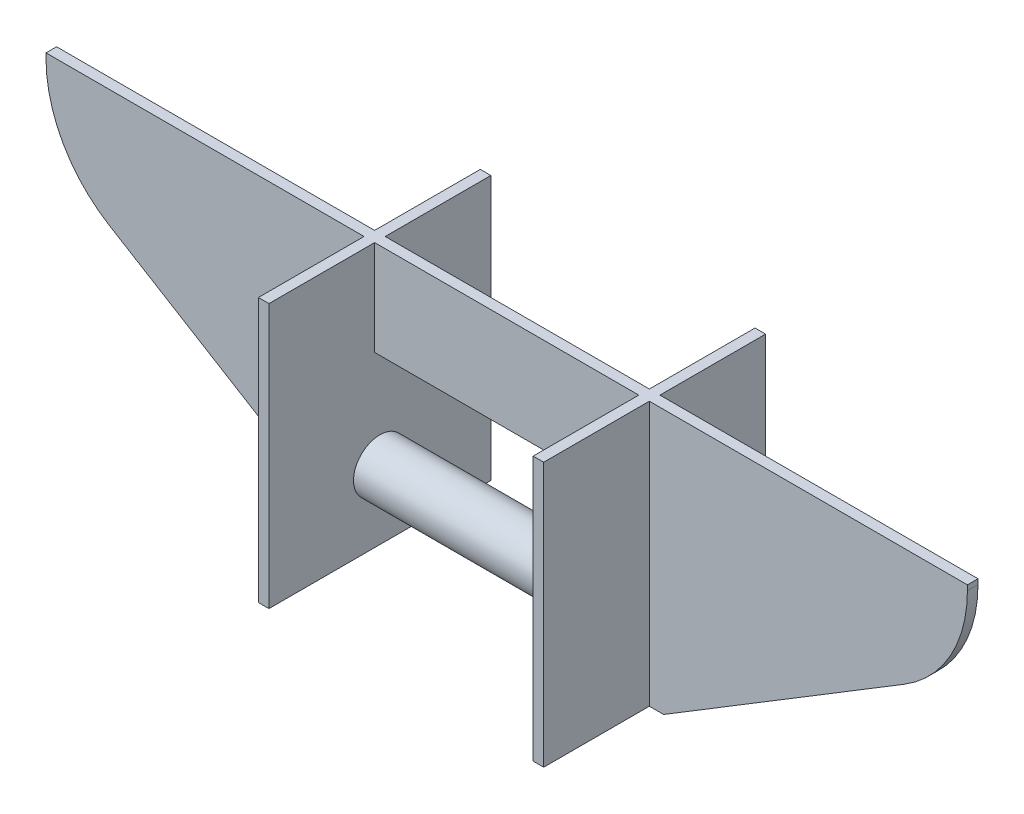
SolidWorks part; units mm, degrees
ref_plane "Front" through (0, 0, 0) normal (0, 0, 1) x (1, 0, 0)
ref_plane "Top" through (0, 0, 0) normal (0, 1, 0) x (1, 0, 0)
ref_plane "Right" through (0, 0, 0) normal (1, 0, 0) x (0, 0, -1)
sketch "Sketch2" plane through (0, 0, 0) normal (0, 0, 1) x (1, 0, 0)
  line L0 (-114.3, 0) -> (-126.238, 0)
  line L1 (-126.238, 0) -> (-241.8046, 70.3449)
  line L2 (-272.288, 124.5865) -> (-272.288, 127)
  line L3 (-114.3, 0) -> (-114.3, 81.28)
  line L4 (-114.3, 81.28) -> (12.7, 81.28)
  line L5 (-272.288, 127) -> (170.688, 127)
  line L6 (-50.8, 127) -> (-50.8, 81.28) construction
  line L7 (12.7, 0) -> (12.7, 81.28)
  line L8 (170.688, 124.5865) -> (170.688, 127)
  line L9 (24.638, 0) -> (140.2046, 70.3449)
  line L10 (12.7, 0) -> (24.638, 0)
  arc A0 (-241.8046, 70.3449) -> (-272.288, 124.5865) centre (-208.788, 124.5865) cw
  arc A1 (140.2046, 70.3449) -> (170.688, 124.5865) centre (107.188, 124.5865) ccw
  point P15 (-272.288, 88.9)
  point P18 (170.688, 88.9)
  dimension "D8" = 63.5
  dimension "D9" = 63.5
  dimension "D1" = 114.3
  dimension "D2" = 11.938
  dimension "D3" = 146.05
  dimension "D4" = 88.9
  dimension "D5" = 38.1
  dimension "D6" = 81.28
  dimension "D7" = 127
extrude "Boss-Extrude1" add sketch "Sketch2" along normal blind 2.54 and the other way blind 2.54
sketch "Sketch3" plane through (0, 0, 2.54) normal (0, 0, 1) x (1, 0, 0)
  line L0 (170.688, 127) -> (-272.288, 127) construction
  line L1 (-114.3, 0) -> (-119.38, 0)
  line L2 (-114.3, 0) -> (-114.3, 127)
  line L3 (-114.3, 127) -> (-119.38, 127)
  line L4 (-119.38, 0) -> (-119.38, 127)
  line L6 (12.7, 0) -> (17.78, 0)
  line L7 (12.7, 0) -> (12.7, 127)
  line L8 (12.7, 127) -> (17.78, 127)
  line L9 (17.78, 0) -> (17.78, 127)
  dimension "D1" = 5.08
  dimension "D2" = 5.08
extrude "Boss-Extrude2" add sketch "Sketch3" along normal blind 50.8 and the other way blind 55.88
sketch "Sketch4" plane through (-114.3, 0, 0) normal (1, 0, 0) x (0, 0, -1)
  line L0 (53.34, 0) -> (-53.34, 0) construction
  circle A0 centre (0, 33.02) radius 12.7
  dimension "D1" = 25.4
  dimension "D2" = 33.02
extrude "Boss-Extrude3" add sketch "Sketch4" along normal up to next
